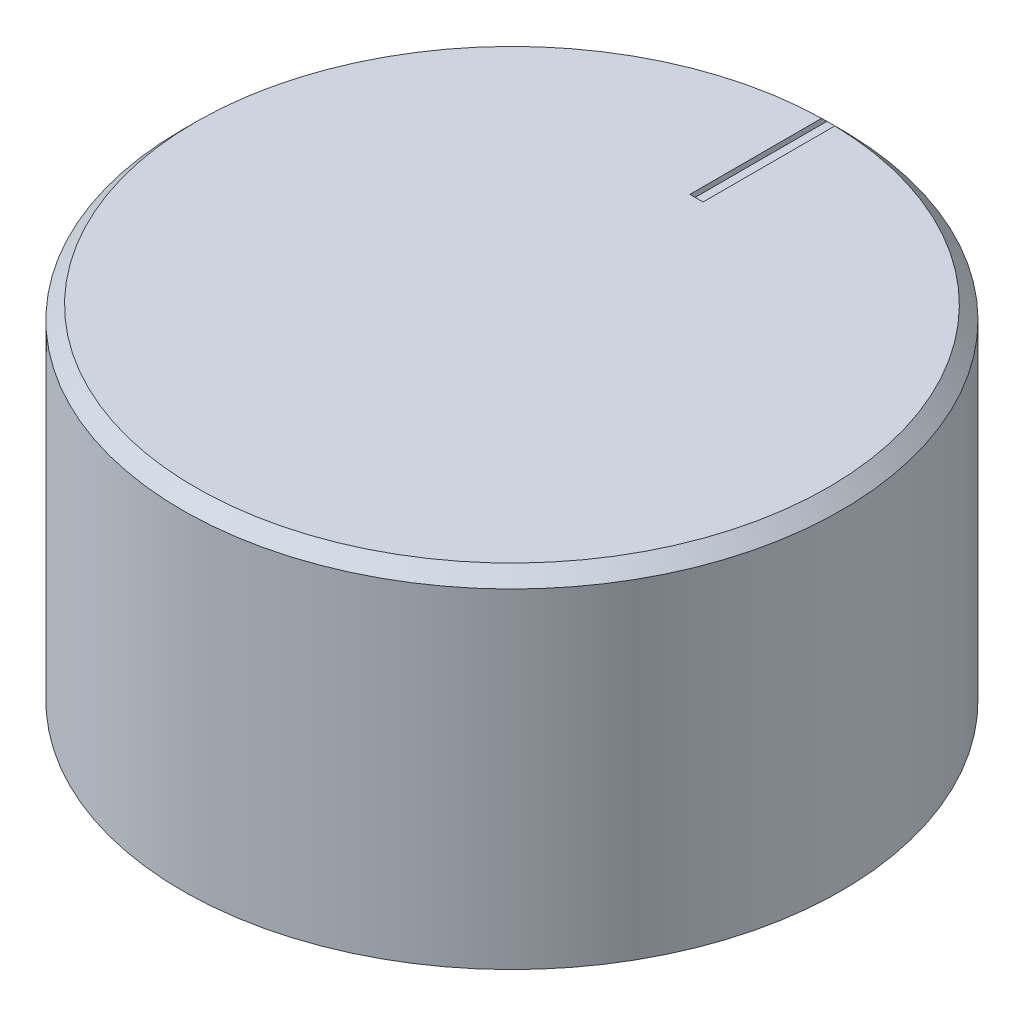
SolidWorks part; units mm, degrees
ref_plane "Alzado" through (0, 0, 0) normal (0, 0, 1) x (1, 0, 0)
ref_plane "Planta" through (0, 0, 0) normal (0, 1, 0) x (1, 0, 0)
ref_plane "Vista lateral" through (0, 0, 0) normal (1, 0, 0) x (0, 0, -1)
ref_plane "Plano1" through (0, 0, 0) normal (0, 0, -1) x (-1, 0, 0)
sketch "Croquis1" plane through (0, 0, 0) normal (0, 0, -1) x (-1, 0, 0)
  line L0 (-12.5, 0) -> (0, 0)
  line L1 (0, 0) -> (0, 13)
  line L2 (0, 13) -> (-12.5, 13)
  line L3 (-12.5, 13) -> (-12.5, 0)
  line L4 (0, 0) -> (0, 13) construction
revolve "Revolución1" add sketch "Croquis1" angle 360 about L4 reverse direction yes
sketch "Croquis2" plane through (0, 13, 0) normal (0, 1, 0) x (-1, 0, 0)
  line L0 (0.25, -12.4975) -> (0.25, -7)
  line L1 (0.25, -7) -> (-0.25, -7)
  line L2 (-0.25, -7) -> (-0.25, -12.4975)
  arc A0 (-0.25, -12.4975) -> (0.25, -12.4975) centre (0, 0) ccw
extrude "Cortar-Extruir1" cut sketch "Croquis2" against normal blind 0.2
hole_wizard "Diámetro de taladro Ø5.0 (5)1" positions "Croquis4" profile "Croquis3" hole size "Ø5.0" standard "Ansi Metric"
sketch "Croquis4" plane through (0, 0, 0) normal (0, -1, 0) x (-1, 0, 0)
  point P0 (0, 0)
sketch "Croquis3" plane through (0, 0, 0) normal (1, 0, 0) x (0, 0, -1)
  line L0 (0, 0) -> (0, 9)
  line L1 (0, 9) -> (2.5, 9)
  line L2 (2.5, 9) -> (2.5, 0)
  line L5 (2.5, 0) -> (0, 0)
  line L10 (0, 9) -> (-2.5, 9) construction
  line L11 (0, -6.35) -> (0, 107.95) construction
  dimension "Diámetro de taladro" = 5
  dimension "Profundidad de taladro" = 9
  dimension "Ángulo de perforador" = 180
chamfer "Chaflán1" distance 0.2 angle 45 1 edges at (0, 13, 12.5)
sketch "Croquis5" plane through (0, 13, 0) normal (0, 1, 0) x (-1, 0, 0)
  line L0 (0.25, -7) -> (-0.25, -7)
  line L1 (-0.25, -12.4975) -> (-0.25, -7)
  line L2 (0.25, -7) -> (0.25, -12.4975)
  arc A0 (0.25, -12.4975) -> (-0.25, -12.4975) centre (0, 0) ccw
  circle A1 centre (0, 0) radius 2.5
extrude "Saliente-Extruir1" add sketch "Croquis5" against normal blind 10
chamfer "Chaflán2" distance 0.5 angle 45 1 edges at (0, 13, 12.5)
